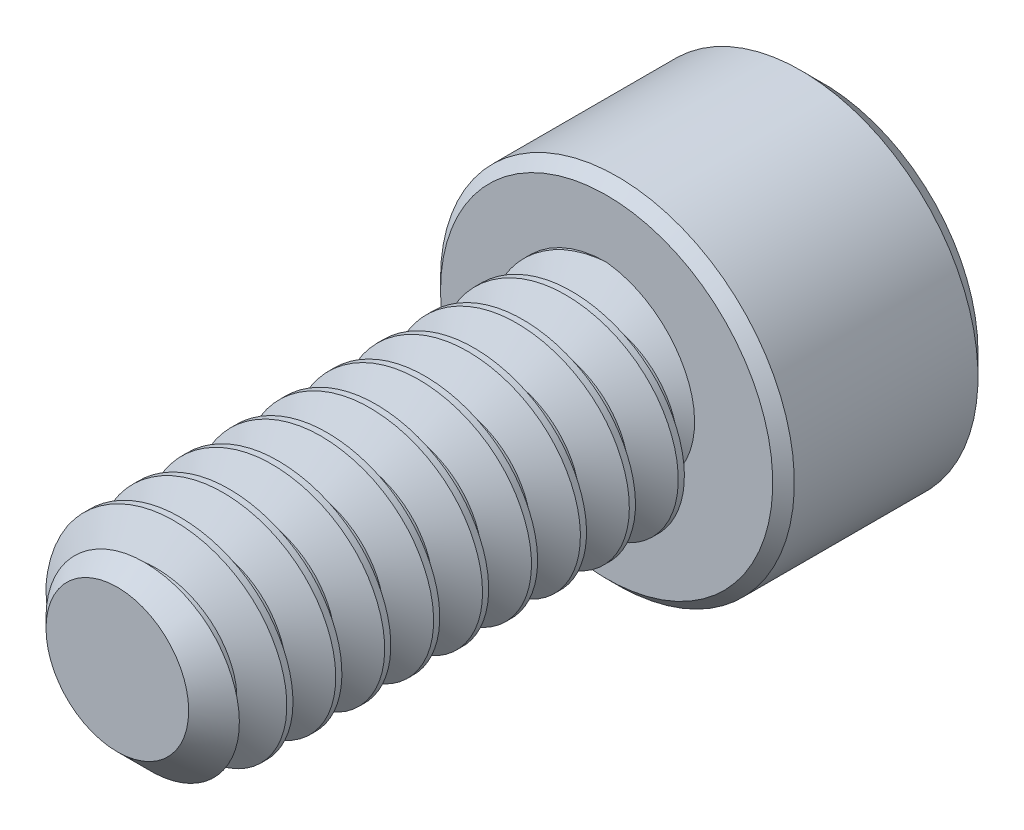
SolidWorks part; units mm, degrees
ref_plane "Front Plane" through (0, 0, 0) normal (0, 0, 1) x (1, 0, 0)
ref_plane "Top Plane" through (0, 0, 0) normal (0, 1, 0) x (1, 0, 0)
ref_plane "Right Plane" through (0, 0, 0) normal (1, 0, 0) x (0, 0, -1)
sketch "Sketch1" plane through (0, 0, 0) normal (0, 0, 1) x (1, 0, 0)
  line L0 (0, 1.7526) -> (0, -1.7526) construction
  circle A0 centre (0, 0) radius 1.7526
  dimension "OD" = 3.5052
extrude "Extrude1" add sketch "Sketch1" against normal blind 7.9375
sketch "Sketch2" plane through (0, 0, 0) normal (0, 0, 1) x (1, 0, 0)
  circle A0 centre (0, 0) radius 1.7526 construction
  circle A1 centre (0, 0) radius 1.7526
curve "Helix/Spiral1" pitch 0.7937 height 8.7312 turns 11 parameters "pitch"=0.7937
chamfer "Chamfer3" distance 0.5953 angle 45 1 edges at (1.7526, 0, 0)
sketch "Sketch3" plane through (0, 0, 0) normal (1, 0, 0) x (0, 0, -1)
  line L0 (-0.6945, 1.7526) -> (-0.3969, 1.237)
  line L1 (-0.3969, 1.237) -> (-0.2977, 1.237)
  line L2 (-0.2977, 1.237) -> (0, 1.7526)
  line L3 (-0.6945, 1.7526) -> (0, 1.7526)
  line L4 (-0.3473, 1.7526) -> (-0.3473, 1.237) construction
  line L5 (-0.5457, 1.4948) -> (-0.1488, 1.4948) construction
  line L6 (0, 1.7526) -> (0, -1.7526) construction
  dimension "D1" = 0.0992
  dimension "D2" = 0.3969
  dimension "D3" = 60
sweep "Cut-Sweep1" cut profiles "Sketch3" path "Helix/Spiral1"
sketch "Sketch6" plane through (0, 0, -7.9375) normal (0, 0, -1) x (-1, 0, 0)
  circle A0 centre (0, 0) radius 2.8702
  dimension "head dia" = 5.7404
extrude "Extrude2" add sketch "Sketch6" along normal blind 3.5052
sketch "Sketch7" plane through (0, 0, -11.4427) normal (0, 0, -1) x (-1, 0, 0)
  line L1 (0, 1.604) -> (-1.3891, 0.802)
  line L2 (-1.3891, 0.802) -> (-1.3891, -0.802)
  line L3 (-1.3891, -0.802) -> (0, -1.604)
  line L4 (0, -1.604) -> (1.3891, -0.802)
  line L5 (1.3891, -0.802) -> (1.3891, 0.802)
  line L6 (1.3891, 0.802) -> (0, 1.604)
  circle A0 centre (0, 0) radius 1.3891 construction
  dimension "hex dia" = 2.7781
extrude "Cut-Extrude1" cut sketch "Sketch7" against normal blind 2.0836
sketch "Sketch8" plane through (0, 0, -11.4427) normal (0, 0, -1) x (-1, 0, 0)
  circle A0 centre (0, 0) radius 1.604
extrude "Cut-Extrude2" cut sketch "Sketch8" against normal blind 0.3505 draft 45
chamfer "Chamfer1" distance 0.3505 angle 45 1 edges at (-2.8702, 0, -11.4427)
chamfer "Chamfer2" distance 0.1753 angle 45 1 edges at (-2.8702, 0, -7.9375)
sketch "Sketch9" plane through (0, 0, 0) normal (1, 0, 0) x (0, 0, -1)
  line L0 (0, 1.7526) -> (0, -1.7526) construction
  line L1 (4.3656, 1.7526) -> (4.3656, -1.7526) construction
  line L2 (7.9375, 2.8702) -> (7.9375, -2.8702) construction
  line L3 (11.4427, 2.8702) -> (11.4427, -2.8702) construction
  line L4 (11.4427, 0) -> (0, 0) construction
  dimension "D1" = 4.3656
  dimension "D2" = 3.5052
  dimension "D3" = 5.7404
  dimension "D4" = 7.9375
equation "\"D3@Helix/Spiral1\" = \"screw length@Extrude1\"+\"pitch@Helix/Spiral1\""
equation "\"D1@Sketch3\" = \"pitch@Helix/Spiral1\"*.125"
equation "\"D2@Sketch3\" = \"pitch@Helix/Spiral1\"*.5"
equation "\"D1@Cut-Extrude1\" = \"hex dia@Sketch7\"*.75"
equation "\"D1@Chamfer1\" = \"head depth@Extrude2\"/10"
equation "\"D1@Sketch9\" = \"pitch@Helix/Spiral1\"*5.5"
equation "\"D1@Chamfer2\" = \"D1@Chamfer1\"/2"
equation "\"D1@Cut-Extrude2\" = \"D1@Chamfer2\"*2"
equation "\"D1@Chamfer3\" = \"pitch@Helix/Spiral1\"*.750"
equation "\"D2@Sketch9\" = \"head depth@Extrude2\""
equation "\"D3@Sketch9\" = \"head dia@Sketch6\""
equation "\"D4@Sketch9\" = \"screw length@Extrude1\""
